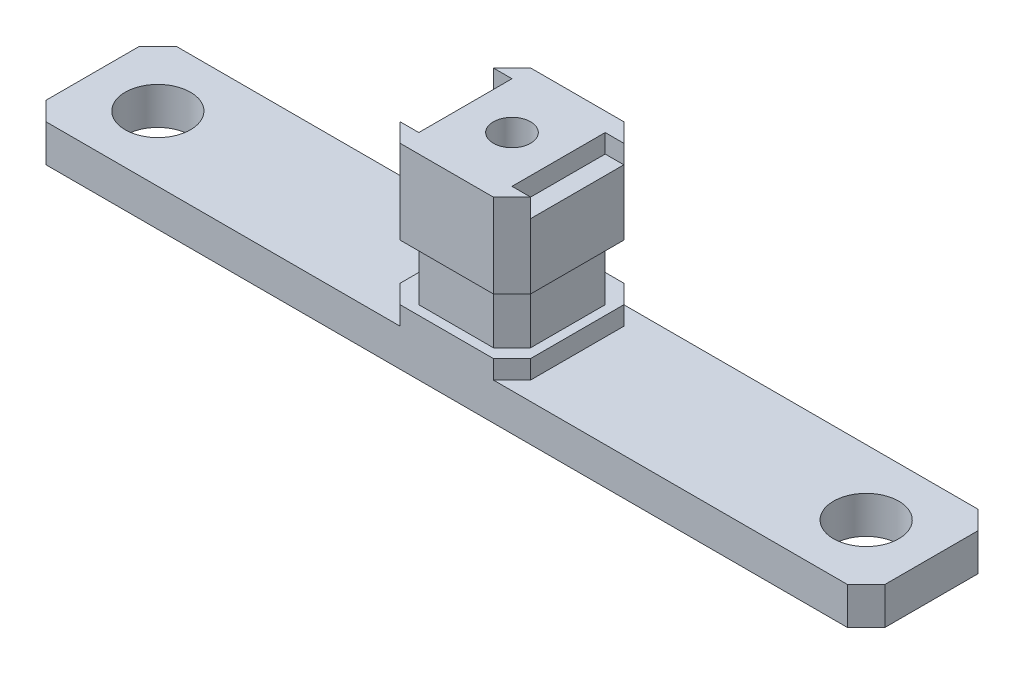
SolidWorks part; units mm, degrees
material "Plain Carbon Steel"
ref_plane "Front Plane" through (0, 0, 0) normal (0, 0, 1) x (1, 0, 0)
ref_plane "Top Plane" through (0, 0, 0) normal (0, 1, 0) x (1, 0, 0)
ref_plane "Right Plane" through (0, 0, 0) normal (1, 0, 0) x (0, 0, -1)
sketch "Sketch1" plane through (0, 0, 0) normal (0, 1, 0) x (1, 0, 0)
  line L1 (-45, -7) -> (45, -7)
  line L2 (-45, -7) -> (-45, 7)
  line L3 (-45, 7) -> (45, 7)
  line L4 (45, -7) -> (45, 7)
  line L5 (-45, -7) -> (45, 7) construction
  line L6 (-45, 7) -> (45, -7) construction
  circle A0 centre (-38, 0) radius 3.5
  circle A1 centre (38, 0) radius 3.5
  circle A2 centre (0, 0) radius 2
  point P0 (0, 0)
  dimension "D3" = 7
  dimension "D4" = 7
  dimension "D7" = 4
  dimension "D1" = 90
  dimension "D2" = 14
  dimension "D5" = 7
  dimension "D6" = 7
extrude "Boss-Extrude1" add sketch "Sketch1" along normal blind 4 contours L1 L4 L3 L2 A2 A1 A0 | A2 region at (-44.0892, 0, 0) region at (0, 0, 0)
sketch "Sketch2" plane through (0, 4, 0) normal (0, 1, 0) x (1, 0, 0)
  line L0 (-45, 7) -> (45, 7) construction
  line L1 (-7, -7) -> (7, -7)
  line L2 (-7, -7) -> (-7, 7)
  line L3 (-7, 7) -> (7, 7)
  line L4 (7, -7) -> (7, 7)
  line L5 (-7, -7) -> (7, 7) construction
  line L6 (-7, 7) -> (7, -7) construction
  point P0 (0, 0)
  dimension "D1" = 14
extrude "Boss-Extrude2" add sketch "Sketch2" along normal blind 2
sketch "Sketch3" plane through (0, 6, 0) normal (0, 1, 0) x (1, 0, 0)
  line L1 (-6, 6) -> (6, 6)
  line L2 (-6, 6) -> (-6, -6)
  line L3 (-6, -6) -> (6, -6)
  line L4 (6, 6) -> (6, -6)
  line L5 (-6, 6) -> (6, -6) construction
  line L6 (-6, -6) -> (6, 6) construction
  point P0 (0, 0)
  dimension "D1" = 12
extrude "Boss-Extrude3" add sketch "Sketch3" along normal blind 6
sketch "Sketch4" plane through (0, 12, 0) normal (0, 1, 0) x (1, 0, 0)
  line L0 (7, 7) -> (45, 7) construction
  line L1 (-7, -7) -> (7, -7)
  line L2 (-7, -7) -> (-7, 7)
  line L3 (-7, 7) -> (7, 7)
  line L4 (7, -7) -> (7, 7)
  line L5 (-7, -7) -> (7, 7) construction
  line L6 (-7, 7) -> (7, -7) construction
  line L7 (7, -7) -> (7, 7) construction
  point P0 (0, 0)
  dimension "D1" = 14
extrude "Boss-Extrude4" add sketch "Sketch4" along normal blind 9
sketch "Sketch5" plane through (0, 21, 0) normal (0, 1, 0) x (1, 0, 0)
  line L0 (-7, 7) -> (-7, -7) construction
  line L1 (-7, 5) -> (-5, 5)
  line L2 (-7, 5) -> (-7, -5)
  line L3 (-7, -5) -> (-5, -5)
  line L4 (-5, 5) -> (-5, -5)
  line L5 (7, -7) -> (7, 7) construction
  line L6 (5, 5) -> (7, 5)
  line L7 (5, 5) -> (5, -5)
  line L8 (5, -5) -> (7, -5)
  line L9 (7, 5) -> (7, -5)
  line L10 (-7, 0) -> (7, 0) construction
  dimension "D1" = 10
  dimension "D2" = 2
  dimension "D3" = 2
sketch "Sketch6" plane through (0, 21, 0) normal (0, 1, 0) x (1, 0, 0)
  circle A0 centre (0, 0) radius 2
  dimension "D1" = 4
extrude "Cut-Extrude1" cut sketch "Sketch6" against normal up to surface (9 mm away) up to face at (0, 12, 0)
sketch "Sketch8" plane through (0, 12, 0) normal (0, 1, 0) x (1, 0, 0)
  circle A0 centre (0, 0) radius 4
  circle M2 centre (0, 0) radius 2
  dimension "D1" = 8
extrude "Cut-Extrude2" cut sketch "Sketch8" against normal through all contours A0 M2 | M2 region at (-3.8869, 12, 0) region at (0, 12, 0)
chamfer "Chamfer1" distance 2 angle 45 15 edges at (7, 5, 7) (6, 9, 6) (7, 16.5, 7) (7, 16.5, -7) (7, 5, -7) (-7, 5, 7) (-7, 5, -7) (-6, 9, -6) (-6, 9, 6) (-7, 16.5, 7) (45, 2, 7) (-45, 2, 7) (-45, 2, -7) (45, 2, -7) (-7, 16.5, -7)
chamfer "Chamfer2" distance 2 angle 45 1 edges at (0, 12, -2)
extrude "Cut-Extrude3" cut sketch "Sketch5" against normal blind 2
chamfer "Chamfer3" distance 2 angle 45 1 edges at (6, 9, -6)
